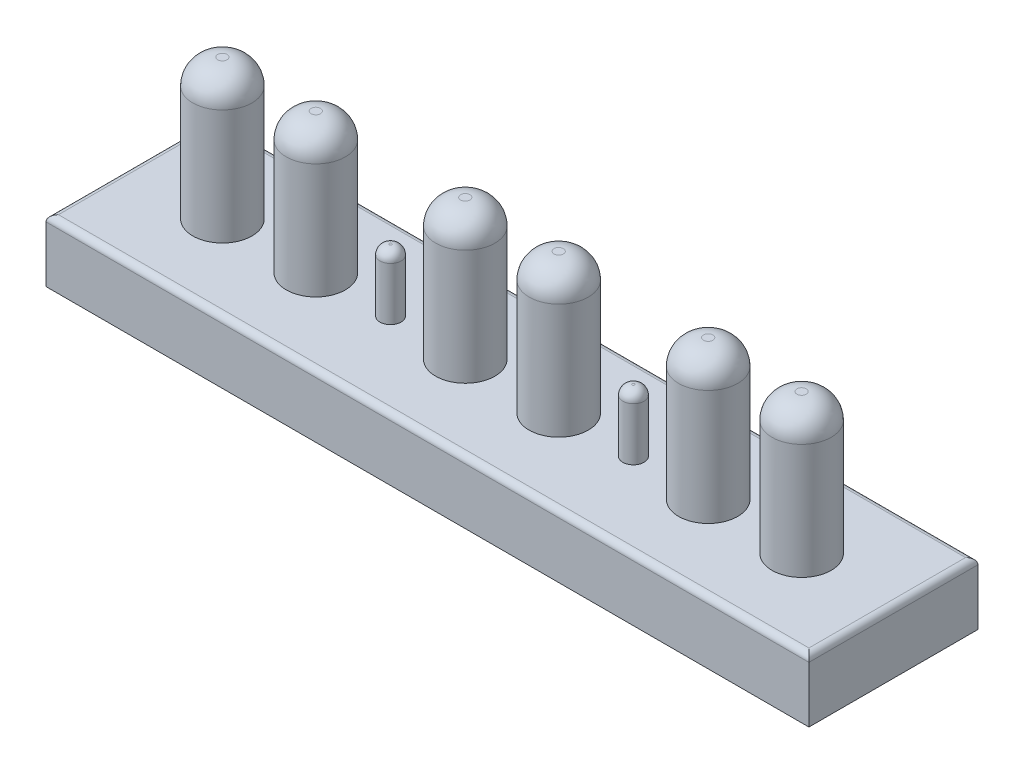
SolidWorks part; units mm, degrees
other "Marquage1"
sketch "Esquisse3"
ref_plane "Front Plane" through (0, 0, 0) normal (0, 0, 1) x (1, 0, 0)
ref_plane "Top Plane" through (0, 0, 0) normal (0, 1, 0) x (1, 0, 0)
ref_plane "Right Plane" through (0, 0, 0) normal (1, 0, 0) x (0, 0, -1)
sketch "Esquisse2" plane through (0, 0, 0) normal (0, 1, 0) x (1, 0, 0)
  line L0 (164.7492, 0) -> (-148.4452, 0) construction
  circle A0 centre (32.4575, 0) radius 9.5
  circle A1 centre (62.4575, 0) radius 9.5
  circle A2 centre (-123.5425, 0) radius 9.5
  circle A3 centre (-93.5425, 0) radius 9.5
  circle A4 centre (-45.5425, 0) radius 9.5
  circle A5 centre (-15.5425, 0) radius 9.5
  circle A6 centre (-69.5425, 0) radius 3.4
  circle A7 centre (8.4575, 0) radius 3.4
  dimension "D1" = 30
  dimension "D2" = 30
  dimension "D3" = 24
  dimension "D4" = 24
  dimension "D5" = 30
  dimension "D6" = 24
  dimension "D7" = 24
extrude "Boss.-Extru.1" add sketch "Esquisse2" along normal blind 45 contours A1 | A0 | A2 | A5 | A4 | A3
extrude "Boss.-Extru.2" add sketch "Esquisse2<4>" along normal blind 20
sketch "Esquisse2<4>" plane through (0, 0, 0) normal (0, 1, 0) x (1, 0, 0) same geometry as "Esquisse2"
fillet "Congé3" radius 8 1 edges at (-123.5425, 45, 9.5)
fillet "Congé4" radius 8 1 edges at (-93.5425, 45, 9.5)
fillet "Congé5" radius 8 1 edges at (-45.5425, 45, 9.5)
fillet "Congé6" radius 8 1 edges at (-15.5425, 45, 9.5)
fillet "Congé7" radius 8 1 edges at (32.4575, 45, 9.5)
fillet "Congé8" radius 8 1 edges at (62.4575, 45, 9.5)
fillet "Congé10" radius 3 1 edges at (-69.5425, 20, 3.4)
sketch "Esquisse4" plane through (0, 0, 0) normal (0, -1, 0) x (-1, 0, 0)
  line L1 (-91.9575, 27.1466) -> (153.0425, 27.1466)
  line L2 (-91.9575, 27.1466) -> (-91.9575, -27.1466)
  line L3 (-91.9575, -27.1466) -> (153.0425, -27.1466)
  line L4 (153.0425, 27.1466) -> (153.0425, -27.1466)
  line L5 (-91.9575, 27.1466) -> (153.0425, -27.1466) construction
  line L6 (-91.9575, -27.1466) -> (153.0425, 27.1466) construction
  circle A3 centre (-62.4575, 0) radius 9.5 construction
  circle A4 centre (123.5425, 0) radius 9.5 construction
  point P0 (0, 0)
  dimension "D1" = 29.5
  dimension "D2" = 29.5
fillet "Congé11" radius 3 1 edges at (8.4575, 20, 3.4)
extrude "Boss.-Extru.3" add sketch "Esquisse4" along normal blind 20
fillet "Congé12" radius 2 4 edges at (-153.0425, 0, 0) (-30.5425, 0, 27.1466) (91.9575, 0, 0) (-30.5425, 0, -27.1466)
